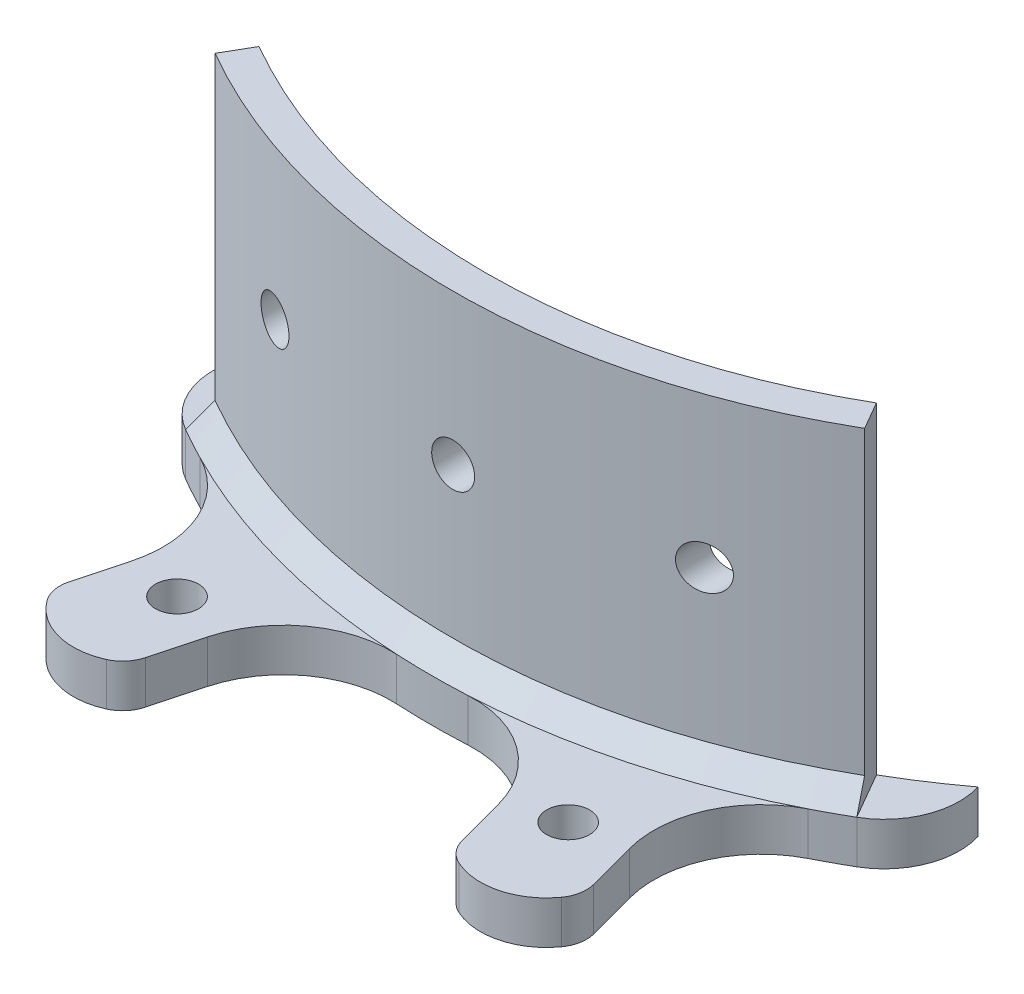
SolidWorks part; units mm, degrees
ref_plane "Front Plane" through (0, 0, 0) normal (0, 0, 1) x (1, 0, 0)
ref_plane "Top Plane" through (0, 0, 0) normal (0, 1, 0) x (1, 0, 0)
ref_plane "Right Plane" through (0, 0, 0) normal (1, 0, 0) x (0, 0, -1)
sketch "Sketch1" plane through (0, 0, 0) normal (0, 1, 0) x (1, 0, 0)
  line L0 (0, 0) -> (0, -54.5) construction
  line L1 (0, 0) -> (0, 55) construction
  line L2 (0, 0) -> (-27.25, -47.1984) construction
  line L3 (0, 0) -> (27.25, -47.1984) construction
  line L4 (-27.25, -47.1984) -> (-25.25, -43.7343)
  line L5 (25.25, -43.7343) -> (27.25, -47.1984)
  arc A0 (-27.25, -47.1984) -> (27.25, -47.1984) centre (0, 0) ccw
  arc A1 (-25.25, -43.7343) -> (25.25, -43.7343) centre (0, 0) ccw
  dimension "D1" = 54.5
  dimension "D2" = 55
  dimension "D3" = 150
  dimension "D4" = 54.5
  dimension "D5" = 4
extrude "Boss-Extrude1" add sketch "Sketch1" along normal blind 10 contours A1 L4 A0 L5
sketch "Sketch3" plane through (0, 0, 0) normal (0, -1, 0) x (1, 0, 0)
  line L0 (0, 0) -> (-27.25, 47.1984) construction
  line L1 (-27.25, 47.1984) -> (27.25, 47.1984) construction
  line L2 (27.25, 47.1984) -> (0, 0) construction
  line L3 (-30.25, 52.3945) -> (-28.75, 49.7965)
  line L4 (28.75, 49.7965) -> (30.25, 52.3945)
  arc A0 (-27.25, 47.1984) -> (27.25, 47.1984) centre (0, 0) cw construction
  arc A1 (-28.75, 49.7965) -> (28.75, 49.7965) centre (0, 0) cw
  arc A2 (-30.25, 52.3945) -> (30.25, 52.3945) centre (0, 0) cw
  dimension "D1" = 3
  dimension "D2" = 3
extrude "Boss-Extrude2" add sketch "Sketch3" against normal blind 30 separate body
sketch "Sketch4" plane through (0, 0, 0) normal (0, -1, 0) x (1, 0, 0)
  line L0 (0, 0) -> (-27.25, 47.1984) construction
  line L1 (-27.25, 47.1984) -> (27.25, 47.1984) construction
  line L2 (27.25, 47.1984) -> (0, 0) construction
  arc A0 (-27.25, 47.1984) -> (27.25, 47.1984) centre (0, 0) cw construction
  arc A1 (-24.25, 42.0022) -> (24.25, 42.0022) centre (0, 0) cw
  arc A2 (-31.25, 54.1266) -> (31.25, 54.1266) centre (0, 0) cw
  arc A3 (-31.25, 54.1266) -> (-24.25, 42.0022) centre (-27.75, 48.0644) ccw
  arc A4 (31.25, 54.1266) -> (24.25, 42.0022) centre (27.75, 48.0644) cw
  dimension "D1" = 6
  dimension "D2" = 8
extrude "Boss-Extrude3" add sketch "Sketch4" along normal blind 4
chamfer "Chamfer1" distance 2 angle 45 2 edges at (0, 0, 60.5) (0, 0, 50.5)
sketch "Sketch5" plane through (0, 0, 0) normal (0, 0, 1) x (1, 0, 0)
  line L0 (-30.25, 16) -> (30.25, 16) construction
  line L1 (-30.25, 30) -> (-30.25, 2) construction
  line L2 (30.25, 30) -> (30.25, 2) construction
  line L3 (0, 16) -> (0, 5.2868) construction
  circle A0 centre (0, 16) radius 2
  circle A1 centre (-20, 16) radius 2
  circle A2 centre (20, 16) radius 2
  dimension "D1" = 4
  dimension "D2" = 4
  dimension "D3" = 20
extrude "Cut-Extrude1" cut sketch "Sketch5" against normal through all both and the other way through all
sketch "Sketch6" plane through (0, -4, 0) normal (0, -1, 0) x (1, 0, 0)
  line L0 (0, 0) -> (31.25, 54.1266) construction
  line L1 (31.25, 54.1266) -> (0, 62.5) construction
  line L2 (0, 62.5) -> (-31.25, 54.1266) construction
  line L3 (-31.25, 54.1266) -> (0, 0) construction
  line L4 (15.625, 58.3133) -> (18.9896, 70.8703) construction
  line L5 (20.954, 58.8828) -> (24.4147, 71.7982)
  line L6 (11.2947, 61.471) -> (14.7554, 74.3864)
  line L7 (20.4546, 57.0192) -> (23.8193, 69.5762) construction
  line L8 (10.7954, 59.6074) -> (14.16, 72.1644) construction
  line L9 (0, 54.5) -> (0, 42.0385) construction
  line L10 (0, 0) -> (0, 54.5) construction
  line L13 (-20.954, 58.8828) -> (-24.4147, 71.7982)
  line L14 (-11.2947, 61.471) -> (-14.7554, 74.3864)
  arc A0 (31.25, 54.1266) -> (-31.25, 54.1266) centre (0, 0) ccw construction
  circle A2 centre (18.2132, 67.9726) radius 2
  arc A3 (20.954, 58.8828) -> (11.2947, 61.471) centre (0, 0) ccw
  arc A4 (1.6355, 64.0592) -> (11.2947, 61.471) centre (-9.6593, 2.5882) cw
  arc A5 (-20.954, 58.8828) -> (-11.2947, 61.471) centre (0, 0) cw
  arc A8 (16.4154, 76.3427) -> (23.9552, 74.3224) centre (18.9541, 70.7378) cw
  arc A9 (24.4147, 71.7982) -> (23.9552, 74.3224) centre (21.5169, 72.5747) ccw
  arc A10 (14.7554, 74.3864) -> (16.4154, 76.3427) centre (17.6532, 73.6099) cw
  circle A11 centre (-18.2132, 67.9726) radius 2
  arc A12 (-20.954, 58.8828) -> (-11.2947, 61.471) centre (0, 0) cw
  arc A13 (-24.4147, 71.7982) -> (-23.9552, 74.3224) centre (-21.5169, 72.5747) cw
  arc A14 (-14.7554, 74.3864) -> (-16.4154, 76.3427) centre (-17.6532, 73.6099) ccw
  arc A15 (-16.4154, 76.3427) -> (-23.9552, 74.3224) centre (-18.9541, 70.7378) ccw
  dimension "D4" = 4
  dimension "D6" = 3
  dimension "D1" = 13
  dimension "D2" = 5
  dimension "D5" = 3
  dimension "D3" = 5
extrude "Boss-Extrude4" add sketch "Sketch6" against normal blind 4
fillet "Fillet1" radius 10 4 edges at (20.954, -2, 58.8828) (11.2947, -2, 61.471) (-20.954, -2, 58.8828) (-11.2947, -2, 61.471)
sketch "Sketch7" plane through (0, 0, 0) normal (0, 1, 0) x (1, 0, 0)
  circle A0 centre (0, 0) radius 57.5
extrude "Cut-Extrude2" cut sketch "Sketch7" against normal through all both and the other way through all
